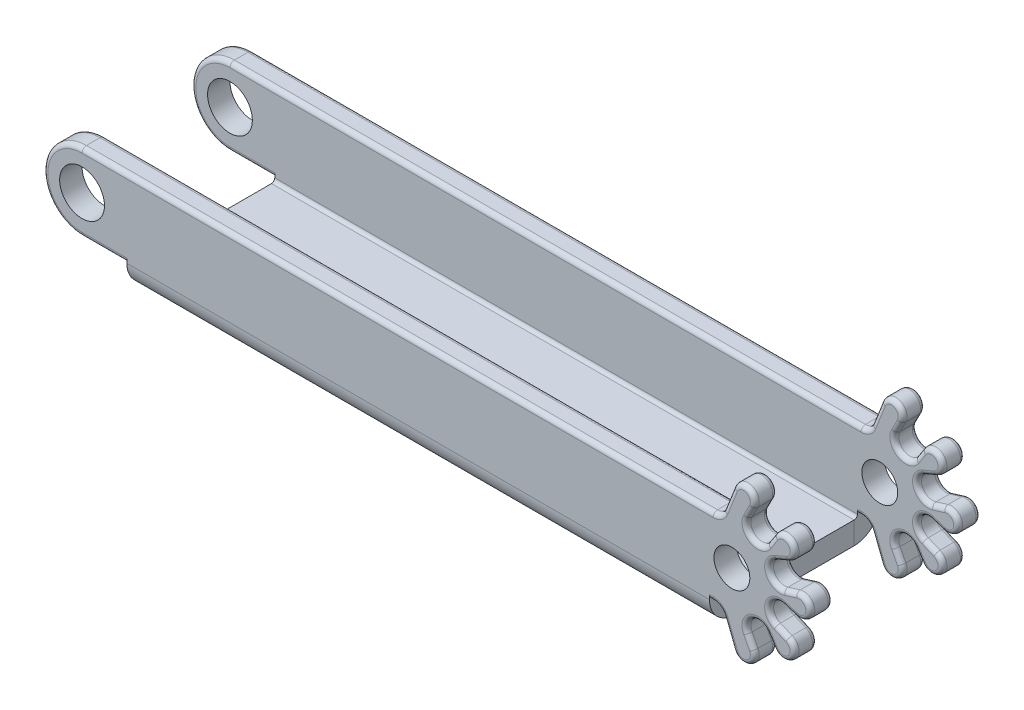
SolidWorks part; units mm, degrees
note: The reader was unsure of these and kept them because the rebuilt part matched: flange length of "Edge-Flange1".
ref_plane "Front Plane" through (0, 0, 0) normal (0, 0, 1) x (1, 0, 0)
ref_plane "Top Plane" through (0, 0, 0) normal (0, 1, 0) x (1, 0, 0)
ref_plane "Right Plane" through (0, 0, 0) normal (1, 0, 0) x (0, 0, -1)
sketch "Sketch1" plane through (0, 0, 0) normal (0, 1, 0) x (1, 0, 0)
  line L1 (-65, 19) -> (65, 19)
  line L2 (-65, 19) -> (-65, -19)
  line L3 (-65, -19) -> (65, -19)
  line L4 (65, 19) -> (65, -19)
  line L5 (-65, 19) -> (65, -19) construction
  line L6 (-65, -19) -> (65, 19) construction
  point P0 (0, 0)
  dimension "D1" = 38
  dimension "D2" = 130
base flange "Base-Flange1" sketch "Sketch1" thickness 5 reverse thickness direction no parameters "D1"=0.7366
edge flange "Edge-Flange1" sketch "Sketch10" flange profiles "Sketch10", "Sketch11" flange angle 90 flange length 23 flange position material inside bend radius 0.7366 thickness 5 relief rectangular parameters "D6"=10, "D8"=1
sketch "Sketch10" plane through (0, 0, 19) normal (0, 0, 1) x (1, 0, 0)
  line L0 (-65, 0) -> (65, 0) construction
  line L1 (-65, 0) -> (65, 0)
  line L2 (-65, 0) -> (-65, 18)
  line L3 (-65, 18) -> (65, 18)
  line L4 (65, 18) -> (65, 0)
sketch "Sketch11" plane through (0, 0, -19) normal (0, 0, -1) x (-1, 0, 0)
  line L0 (-65, 0) -> (65, 0) construction
  line L1 (-65, 0) -> (65, 0)
  line L2 (-65, 0) -> (-65, 18)
  line L3 (-65, 18) -> (65, 18)
  line L4 (65, 18) -> (65, 0)
bend "EdgeBend1" bend radius 0.7366 bend angle 90 parameters "D5"=1
bend "EdgeBend2" bend radius 0.7366 bend angle 90 parameters "D5"=2
sketch "Sketch15" plane through (0, 0, 19) normal (0, 0, 1) x (1, 0, 0)
  line L1 (-65, 18) -> (-65, 0.7366) construction
  line L2 (-75, 18) -> (-65, 18)
  line L3 (-65, 18) -> (-65, 0.7366)
  line L4 (-65, 0.7366) -> (-75, 0.7366)
  arc A0 (-75, 18) -> (-75, 0.7366) centre (-75, 9.3683) ccw
  circle A1 centre (-75, 9.3683) radius 5
  point P8 (-65, 9.3683)
  dimension "D1" = 10
  dimension "D2" = 10
extrude "Boss-Extrude1" add sketch "Sketch15" against normal blind 5 contours A1
mirror "Mirror3" about plane through (0, 0, 0) normal (0, 0, 1) of "Boss-Extrude1"
sketch "Sketch16" plane through (0, 0, 19) normal (0, 0, 1) x (1, 0, 0)
  line L0 (65, 18) -> (67.5, 18)
  line L1 (70, 9.3683) -> (91.4551, -27.793) construction
  line L2 (70, 9.3683) -> (91.4551, 46.5296) construction
  line L3 (35.0206, 9.3683) -> (142.7481, 9.3683) construction
  line L4 (70, 9.3683) -> (104.0826, -3.0368) construction
  line L5 (70, 9.3683) -> (104.0826, 21.7734) construction
  line L6 (70, 9.3683) -> (94.6256, -11.295) construction
  line L7 (70, 9.3683) -> (87.3049, 23.8889) construction
  line L16 (65, 18) -> (65, 0.7366)
  line L18 (65, 0.7366) -> (67.5, 0.7366)
  line L20 (70, 9.3683) -> (74.2698, -14.8467) construction
  line L21 (70, 9.3683) -> (74.0259, 32.2004) construction
  line L22 (73.5275, -1.7358) -> (74.8272, -4.259)
  line L23 (77.8527, 0.7613) -> (79.388, -1.6259)
  line L24 (79.8398, 3.1295) -> (82.4573, 2.032)
  line L25 (81.5479, 7.8226) -> (84.2585, 6.9808)
  line L26 (81.5479, 10.914) -> (84.2585, 11.7558)
  line L27 (79.8398, 15.6071) -> (82.4573, 16.7046)
  line L28 (77.8527, 17.9753) -> (79.388, 20.3625)
  line L29 (73.5275, 20.4724) -> (74.8272, 22.9956)
  line L30 (70.2786, 25.0564) -> (67.5, 18)
  line L31 (67.5, 0.7366) -> (70.2786, -6.3198)
  circle A0 centre (70, 9.3683) radius 17.5 construction
  circle A1 centre (70, 9.3683) radius 14 construction
  circle A2 centre (70, 9.3683) radius 15 construction
  circle A7 centre (70, 9.3683) radius 11.5 construction
  arc A11 (84.2585, 6.9808) -> (84.2585, 11.7558) centre (85, 9.3683) ccw
  arc A12 (79.8398, 15.6071) -> (81.5479, 10.914) centre (80.8065, 13.3015) ccw
  arc A13 (82.4573, 16.7046) -> (79.388, 20.3625) centre (81.4907, 19.0101) ccw
  arc A14 (73.5275, 20.4724) -> (77.8527, 17.9753) centre (75.75, 19.3276) ccw
  arc A15 (81.5479, 7.8226) -> (79.8398, 3.1295) centre (80.8065, 5.4351) ccw
  arc A16 (79.388, -1.6259) -> (82.4573, 2.032) centre (81.4907, -0.2735) ccw
  arc A17 (77.8527, 0.7613) -> (73.5275, -1.7358) centre (75.75, -0.591) ccw
  arc A18 (70.2786, -6.3198) -> (74.8272, -4.259) centre (72.6047, -5.4038) ccw
  arc A19 (74.8272, 22.9956) -> (70.2786, 25.0564) centre (72.6047, 24.1404) ccw
  point P21 (65, 9.3683)
  dimension "D1" = 35
  dimension "D2" = 28
  dimension "D5" = 30
  dimension "D6" = 23
  dimension "D3" = 120
  dimension "D4" = 40
  dimension "D7" = 20
  dimension "D8" = 20
  dimension "D9" = 5
  dimension "D10" = 20
  dimension "D11" = 20
  dimension "D12" = 2.5
extrude "Boss-Extrude2" add sketch "Sketch16" against normal blind 5
sketch "Sketch17" plane through (0, 0, 19) normal (0, 0, 1) x (1, 0, 0)
  circle A0 centre (70, 9.3683) radius 4
  dimension "D1" = 8
extrude "Cut-Extrude2" cut sketch "Sketch17" against normal blind 5 normal cut yes
mirror "Mirror5" about plane through (0, 0, 0) normal (0, 0, 1) of "Cut-Extrude2", "Boss-Extrude2"
fillet "Fillet3" radius 2.5 4 edges at (67.5, 0.7366, -16.5) (67.5, 0.7366, 16.5) (67.5, 18, -16.5) (67.5, 18, 16.5)
fillet "Fillet4" radius 1 100 edges at (74.5, 1.5741, 14) (74.1774, -2.9974, 14) (73.6364, -7.681, 14) (65.3988, 0.7366, 14) (69.2012, 22.3202, 14) (73.6364, 26.4176, 14) (74.1774, 21.734, 14) (74.5, 17.1625, 14) (78.6203, 19.1689, 14) (83.4058, 20.6171, 14) (81.1486, 16.1558, 14) (78.4572, 12.4465, 14) (82.9032, 11.3349, 14) (87.5, 9.3683, 14) (82.9032, 7.4017, 14) (78.4572, 6.2901, 14) (81.1486, 2.5808, 14) (83.4058, -1.8805, 14) (78.6203, -0.4323, 14) (74.5, 1.5741, 19) (78.6203, -0.4323, 19) (83.4058, -1.8805, 19) (81.1486, 2.5808, 19) (78.4572, 6.2901, 19) (82.9032, 7.4017, 19) (87.5, 9.3683, 19) (82.9032, 11.3349, 19) (78.4572, 12.4465, 19) (81.1486, 16.1558, 19) (83.4058, 20.6171, 19) (78.6203, 19.1689, 19) (74.5, 17.1625, 19) (74.1774, 21.734, 19) (73.6364, 26.4176, 19) (69.2012, 22.3202, 19) (65.3988, 0.7366, 19) (73.6364, -7.681, 19) (74.1774, -2.9974, 19) (74.5, 1.5741, -19) (78.6203, -0.4323, -19) (83.4058, -1.8805, -19) (81.1486, 2.5808, -19) (78.4572, 6.2901, -19) (82.9032, 7.4017, -19) (87.5, 9.3683, -19) (82.9032, 11.3349, -19) (78.4572, 12.4465, -19) (81.1486, 16.1558, -19) (83.4058, 20.6171, -19) (78.6203, 19.1689, -19) (74.5, 17.1625, -19) (74.1774, 21.734, -19) (73.6364, 26.4176, -19) (69.2012, 22.3202, -19) (65.3988, 0.7366, -19) (73.6364, -7.681, -19) (74.1774, -2.9974, -19) (74.5, 1.5741, -14) (78.6203, -0.4323, -14) (83.4058, -1.8805, -14) (81.1486, 2.5808, -14) (78.4572, 6.2901, -14) (82.9032, 7.4017, -14) (87.5, 9.3683, -14) (82.9032, 11.3349, -14) (78.4572, 12.4465, -14) (81.1486, 16.1558, -14) (83.4058, 20.6171, -14) (78.6203, 19.1689, -14) (74.5, 17.1625, -14) (74.1774, 21.734, -14) (73.6364, 26.4176, -14) (69.2012, 22.3202, -14) (65.3988, 0.7366, -14) (73.6364, -7.681, -14) (74.1774, -2.9974, -14) (69.2012, -3.5836, -19) (69.2012, -3.5836, -14) (69.2012, -3.5836, 19) (69.2012, -3.5836, 14) (-4.6012, 18, 14) (-4.6012, 18, 19) (67.2047, 0.303, -19) (67.2047, 0.303, -14) (67.2047, 0.303, 19) (67.2047, 0.303, 14) (67.2047, 18.4336, -19) (67.2047, 18.4336, -14) (67.2047, 18.4336, 19) (67.2047, 18.4336, 14) (-4.6012, 18, -19) (-4.6012, 18, -14) (-70, 0.7366, 14) (-83.6317, 9.3683, 14) (-70, 0.7366, 19) (-83.6317, 9.3683, 19) (-70, 0.7366, -14) (-83.6317, 9.3683, -14) (-70, 0.7366, -19) (-83.6317, 9.3683, -19)
sketch "Bend-Lines1" [suppressed] plane through (0, 0, 0) normal (0, 1, 0) x (1, 0, 0)
sketch "Bounding-Box1" [suppressed] plane through (0, 0, 0) normal (0, 1, 0) x (1, 0, 0)
sheet metal parameters "Sheet-Metal1" thickness 5 parameters "D1"=0.7366
flat pattern "Flat-Pattern1" [suppressed]
sketch "Bend-Lines2" plane through (0, 0, 0) normal (0, 1, 0) x (1, 0, 0)
sketch3d "Bounding-Box2" [suppressed]
  line L0 (-72.5, -19, 0) -> (72.5, -19, 0) construction
  line L1 (-72.5, 19, 0) -> (72.5, 19, 0) construction
  line L2 (-72.5, -19, 0) -> (-72.5, 19, 0) construction
  line L3 (72.5, -19, 0) -> (72.5, 19, 0) construction
sheet metal parameters "Sheet-Metal2" thickness 5 parameters "D1"=0.7366
flat pattern "Flat-Pattern1"
sketch "Bend-Lines2" plane through (0, 0, 0) normal (0, 1, 0) x (1, 0, 0)
  line L0 (72.5, 15.8054) -> (-72.5, 15.8054) construction
  line L1 (-72.5, -15.8054) -> (72.5, -15.8054) construction
  line L2 (72.5, 15.8054) -> (-72.5, 15.8054) construction
  line L3 (-72.5, -15.8054) -> (72.5, -15.8054) construction
sketch3d "Bounding-Box2" [suppressed]
  line L0 (72.5, -35.6108, 0) -> (-72.5, -35.6108, 0) construction
  line L1 (72.5, 35.6108, 0) -> (-72.5, 35.6108, 0) construction
  line L2 (72.5, -35.6108, 0) -> (72.5, 35.6108, 0) construction
  line L3 (-72.5, -35.6108, 0) -> (-72.5, 35.6108, 0) construction
bend of the flat pattern "Flatten-<EdgeBend1>1"
bend of the flat pattern "Flatten-<EdgeBend2>1"
sheet metal parameters "Sheet-Metal3" thickness 5 parameters "D1"=0.7366
flat pattern "Flat-Pattern1"
sketch "Bend-Lines2" plane through (0, 0, 0) normal (0, 1, 0) x (1, 0, 0)
  line L0 (67.5, 15.8054) -> (-67.5, 15.8054) construction
  line L1 (-67.5, -15.8054) -> (67.5, -15.8054) construction
  line L2 (67.5, 15.8054) -> (-67.5, 15.8054) construction
  line L3 (-67.5, -15.8054) -> (67.5, -15.8054) construction
sketch3d "Bounding-Box2" [suppressed]
  line L0 (-86.1316, -35.6108, 0) -> (67.5, -35.6108, 0) construction
  line L1 (-86.1316, 35.6108, 0) -> (67.5, 35.6108, 0) construction
  line L2 (-86.1316, -35.6108, 0) -> (-86.1316, 35.6108, 0) construction
  line L3 (67.5, -35.6108, 0) -> (67.5, 35.6108, 0) construction
bend of the flat pattern "Flatten-<EdgeBend1>1"
bend of the flat pattern "Flatten-<EdgeBend2>1"
sheet metal parameters "Sheet-Metal7" thickness 5 parameters "D1"=0.7366
flat pattern "Flat-Pattern1"
sketch "Bend-Lines2" plane through (0, 0, 0) normal (0, 1, 0) x (1, 0, 0)
  line L0 (67.5, 15.8054) -> (-67.5, 15.8054) construction
  line L1 (-67.5, -15.8054) -> (67.5, -15.8054) construction
  line L2 (67.5, 15.8054) -> (-67.5, 15.8054) construction
  line L3 (-67.5, -15.8054) -> (67.5, -15.8054) construction
sketch3d "Bounding-Box2" [suppressed]
  line L0 (-86.1316, -35.6108, 0) -> (67.5, -35.6108, 0) construction
  line L1 (-86.1316, 35.6108, 0) -> (67.5, 35.6108, 0) construction
  line L2 (-86.1316, -35.6108, 0) -> (-86.1316, 35.6108, 0) construction
  line L3 (67.5, -35.6108, 0) -> (67.5, 35.6108, 0) construction
bend of the flat pattern "Flatten-<EdgeBend1>1"
bend of the flat pattern "Flatten-<EdgeBend2>1"
sheet metal parameters "Sheet-Metal8" thickness 5 parameters "D1"=0.7366
flat pattern "Flat-Pattern1"
sketch "Bend-Lines2" plane through (0, 0, 0) normal (0, 1, 0) x (1, 0, 0)
  line L0 (67.5, 15.8054) -> (-67.5, 15.8054) construction
  line L1 (-67.5, -15.8054) -> (67.5, -15.8054) construction
  line L2 (67.5, 15.8054) -> (-67.5, 15.8054) construction
  line L3 (-67.5, -15.8054) -> (67.5, -15.8054) construction
sketch3d "Bounding-Box2" [suppressed]
  line L0 (-86.1316, -42.4695, 0) -> (84.0954, -42.4695, 0) construction
  line L1 (-86.1316, 35.6108, 0) -> (84.0954, 35.6108, 0) construction
  line L2 (-86.1316, -42.4695, 0) -> (-86.1316, 35.6108, 0) construction
  line L3 (84.0954, -42.4695, 0) -> (84.0954, 35.6108, 0) construction
bend of the flat pattern "Flatten-<EdgeBend1>1"
bend of the flat pattern "Flatten-<EdgeBend2>1"
sheet metal parameters "Sheet-Metal9" thickness 5 parameters "D1"=0.7366
flat pattern "Flat-Pattern1"
sketch "Bend-Lines2" plane through (0, 0, 0) normal (0, 1, 0) x (1, 0, 0)
  line L0 (67.5, 15.8054) -> (-67.5, 15.8054) construction
  line L1 (-67.5, -15.8054) -> (67.5, -15.8054) construction
  line L2 (67.5, 15.8054) -> (-67.5, 15.8054) construction
  line L3 (-67.5, -15.8054) -> (67.5, -15.8054) construction
sketch3d "Bounding-Box2" [suppressed]
  line L0 (-86.1316, -42.4695, 0) -> (84.0954, -42.4695, 0) construction
  line L1 (-86.1316, 35.6108, 0) -> (84.0954, 35.6108, 0) construction
  line L2 (-86.1316, -42.4695, 0) -> (-86.1316, 35.6108, 0) construction
  line L3 (84.0954, -42.4695, 0) -> (84.0954, 35.6108, 0) construction
bend of the flat pattern "Flatten-<EdgeBend1>1"
bend of the flat pattern "Flatten-<EdgeBend2>1"
sheet metal parameters "Sheet-Metal10" thickness 5 parameters "D1"=0.7366
flat pattern "Flat-Pattern1"
sketch "Bend-Lines2" plane through (0, 0, 0) normal (0, 1, 0) x (1, 0, 0)
  line L0 (65, 15.8054) -> (-65, 15.8054) construction
  line L1 (-65, -15.8054) -> (65, -15.8054) construction
  line L2 (65, 15.8054) -> (-65, 15.8054) construction
  line L3 (-65, -15.8054) -> (65, -15.8054) construction
sketch3d "Bounding-Box2" [suppressed]
  line L0 (-83.6317, -44.2513, 0) -> (87.5, -44.2513, 0) construction
  line L1 (-83.6317, 44.2513, 0) -> (87.5, 44.2513, 0) construction
  line L2 (-83.6317, -44.2513, 0) -> (-83.6317, 44.2513, 0) construction
  line L3 (87.5, -44.2513, 0) -> (87.5, 44.2513, 0) construction
bend of the flat pattern "Flatten-<EdgeBend1>1"
bend of the flat pattern "Flatten-<EdgeBend2>1"
